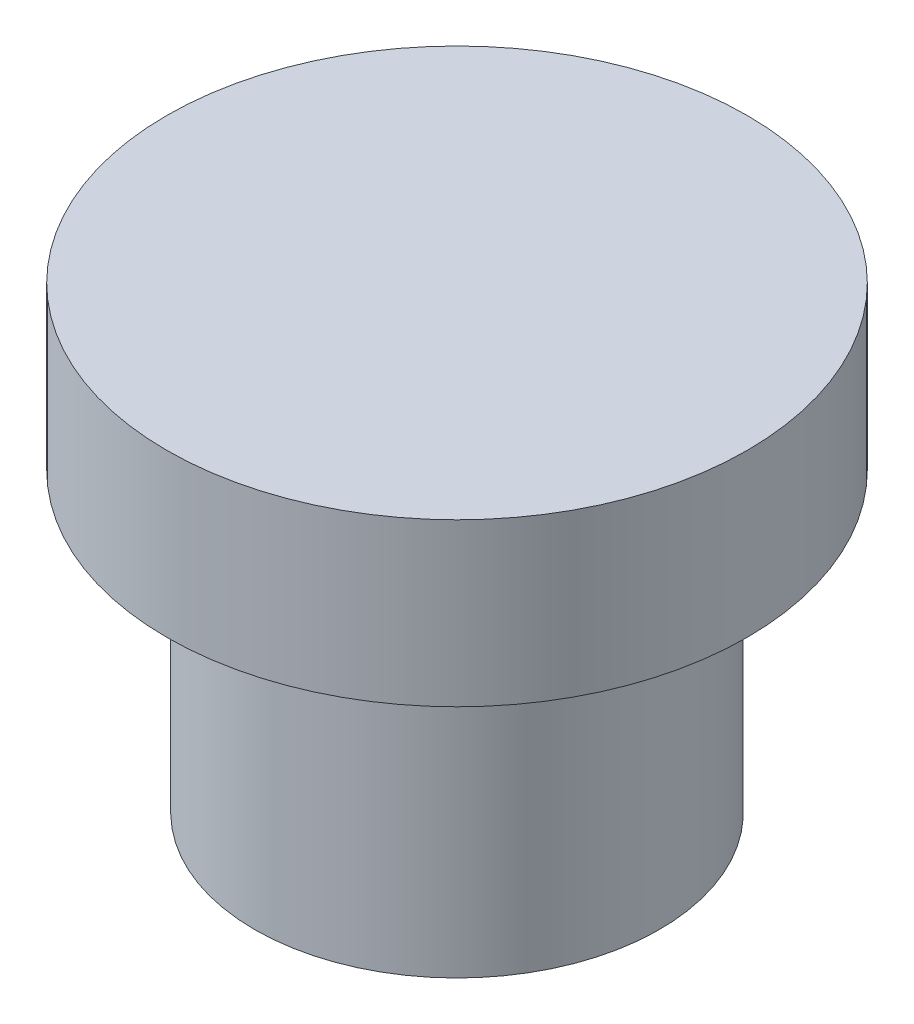
SolidWorks part; units mm, degrees
ref_plane "Front Plane" through (0, 0, 0) normal (0, 0, 1) x (1, 0, 0)
ref_plane "Top Plane" through (0, 0, 0) normal (0, 1, 0) x (1, 0, 0)
ref_plane "Right Plane" through (0, 0, 0) normal (1, 0, 0) x (0, 0, -1)
sketch "Sketch1" plane through (0, 0, 0) normal (0, 1, 0) x (1, 0, 0)
  circle A0 centre (0, 0) radius 7.5
  dimension "D1" = 15
extrude "Boss-Extrude1" add sketch "Sketch1" along normal blind 11
sketch "Sketch2" plane through (0, 11, 0) normal (0, 1, 0) x (1, 0, 0)
  circle A0 centre (0, 0) radius 10.75
  dimension "D1" = 21.5
extrude "Boss-Extrude2" add sketch "Sketch2" along normal blind 6
